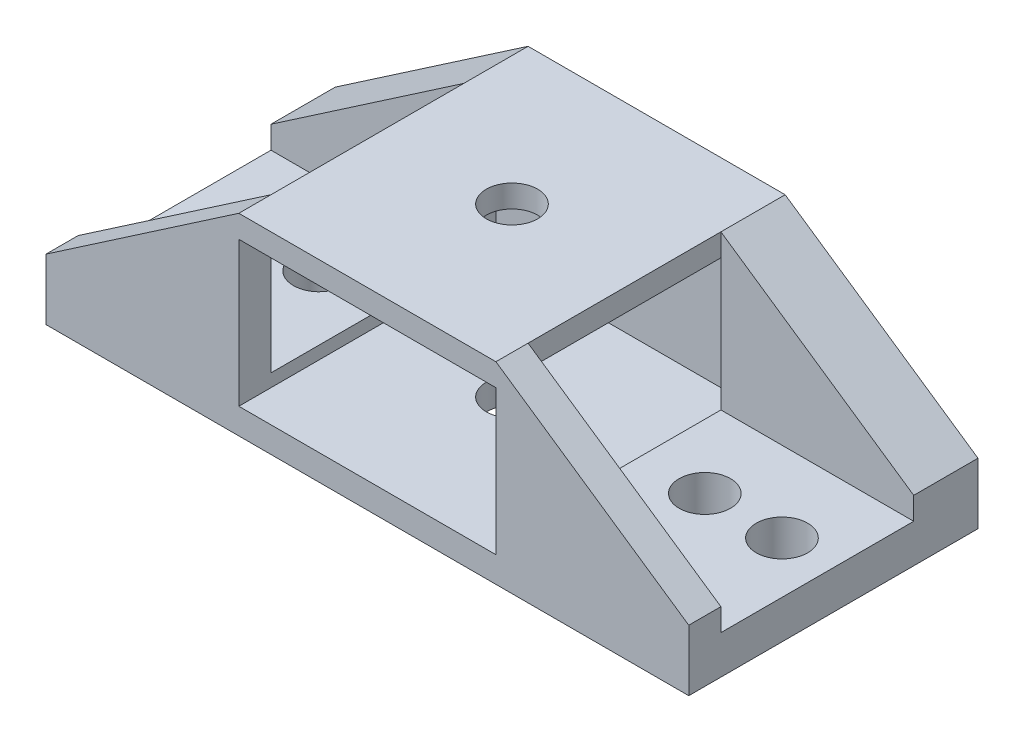
SolidWorks part; units mm, degrees
ref_plane "Front Plane" through (0, 0, 0) normal (0, 0, 1) x (1, 0, 0)
ref_plane "Top Plane" through (0, 0, 0) normal (0, 1, 0) x (1, 0, 0)
ref_plane "Right Plane" through (0, 0, 0) normal (1, 0, 0) x (0, 0, -1)
sketch "Sketch1" plane through (0, 0, 0) normal (0, 1, 0) x (1, 0, 0)
  line L0 (0, 11.25) -> (50, 11.25) construction
  line L1 (0, 0) -> (50, 0)
  line L2 (0, 0) -> (0, 22.5)
  line L3 (0, 22.5) -> (50, 22.5)
  line L4 (50, 0) -> (50, 22.5)
  line L5 (15, 22.5) -> (35, 22.5)
  line L6 (15, 22.5) -> (15, 0)
  line L7 (15, 0) -> (35, 0)
  line L8 (35, 22.5) -> (35, 0)
  circle A0 centre (4, 11.25) radius 2
  circle A1 centre (10, 11.25) radius 2
  circle A2 centre (40, 11.25) radius 2
  circle A3 centre (46, 11.25) radius 2
  point P19 (69.6045, -7.2844)
  dimension "D5" = 4
  dimension "D6" = 30
  dimension "D7" = 4
  dimension "D8" = 4
  dimension "D2" = 50
  dimension "D3" = 20
  dimension "D4" = 15
  dimension "D9" = 6
  dimension "D10" = 22.5
extrude "Boss-Extrude1" add sketch "Sketch1" along normal blind 3 contours L2 L0 A0 A1 L6 L3 | L0 L2 L1 L6 A1 A0 | L0 L6 L1 L8 | L6 L0 L8 L3 | L0 L8 L1 L4 A3 A2 | L8 L0 A2 A3 L4 L3 region at (42.4598, 0, -17.2593) region at (42.4598, 0, -5.2407) region at (25, 0, -5.625) region at (25, 0, -16.875) region at (7.5402, 0, -5.2407) region at (7.5402, 0, -17.2593)
extrude "Boss-Extrude2" add sketch "Sketch1<3>" along normal blind 15 contours L0 L6 L1 L8 | L6 L0 L8 L3 region at (25, 0, -5.625) region at (25, 0, -16.875)
sketch "Sketch1<3>" plane through (0, 0, 0) normal (0, 1, 0) x (1, 0, 0) same geometry as "Sketch1"
sketch "Sketch2" plane through (0, 0, 0) normal (0, 0, 1) x (1, 0, 0)
  line L0 (15, 13.25) -> (35, 13.25)
  line L1 (15, 15) -> (35, 15)
  line L2 (15, 15) -> (15, 3)
  line L3 (15, 3) -> (35, 3)
  line L4 (35, 15) -> (35, 3)
  line L6 (15, 3) -> (35, 3)
  line L7 (15, 3) -> (15, 2)
  line L8 (15, 2) -> (35, 2)
  line L9 (35, 3) -> (35, 2)
  line M8 (15, 15) -> (15, 3)
  dimension "D1" = 1.75
  dimension "D2" = 1
extrude "Cut-Extrude1" cut sketch "Sketch2" against normal blind 20 contours L4 L0 M8 | L9 L3 L7 L8 region at (25, 8.125, 0) region at (25, 2.5, 0)
sketch "Sketch3" plane through (0, 3, 0) normal (0, 1, 0) x (1, 0, 0)
  line L0 (15, 20) -> (15, 22.5) construction
  line L1 (0, 22.5) -> (15, 22.5)
  line L2 (0, 22.5) -> (0, 13)
  line L3 (15, 2.5) -> (0, 2.5)
  line L4 (15, 22.5) -> (15, 13)
  line L5 (25, 17.5) -> (25, 0) construction
  line L6 (35, 22.5) -> (35, 13)
  line L7 (50, 22.5) -> (35, 22.5)
  line L8 (50, 22.5) -> (50, 13)
  line L13 (15, 0) -> (35, 0)
  line L14 (35, 0) -> (35, 17.5)
  line L15 (35, 17.5) -> (15, 17.5)
  line L16 (15, 17.5) -> (15, 0)
  line L17 (0, 0) -> (0, 22.5) construction
  line L18 (15, 17.5) -> (0, 17.5)
  line L19 (0, 0) -> (15, 0)
  line L20 (35, 17.5) -> (50, 17.5)
  line L21 (0, 2.5) -> (0, 0)
  line L22 (50, 2.5) -> (50, 0)
  line L23 (50, 0) -> (35, 0)
  line L24 (35, 2.5) -> (50, 2.5)
  line M12 (0, 0) -> (15, 0)
  line M13 (15, 20) -> (15, 22.5)
  line M14 (15, 22.5) -> (0, 22.5)
  line M15 (0, 22.5) -> (0, 0)
  dimension "D2" = 2.5
  dimension "D3" = 17.5
  dimension "D1" = 20
extrude "Boss-Extrude3" add sketch "Sketch3" along normal up to surface (12 mm away) contours L18 L4 M14 M15 | L3 M13 M15 M12 | L6 L20 L8 L7 | L24 L14 L23 L22 region at (42.5, 3, -20) region at (7.5, 3, -20) region at (7.5, 3, -1.25) region at (42.5, 3, -1.25) up to face at (25, 15, -11.25)
sketch "Sketch4" plane through (0, 0, 0) normal (0, 0, 1) x (1, 0, 0)
  line L0 (15, 15) -> (0, 4.75)
  line L1 (0, 15) -> (50, 15) construction
  line L2 (25, 13.25) -> (25, 4.75) construction
  line L3 (0, 15) -> (0, 0) construction
  line L4 (35, 15) -> (50, 4.75)
  line L5 (50, 15) -> (50, 0) construction
  line L12 (35, 13.25) -> (15, 13.25)
  line L24 (35, 13.25) -> (15, 13.25)
  line L32 (15, 13.25) -> (15, 2)
  line L35 (15, 13.25) -> (15, 2)
  line L36 (15, 2) -> (35, 2)
  line L37 (15, 2) -> (35, 2)
  line L38 (35, 2) -> (35, 13.25)
  line L39 (35, 2) -> (35, 13.25)
  line M15 (50, 0) -> (50, 15)
  line M16 (50, 15) -> (0, 15)
  line M17 (0, 15) -> (0, 0)
  dimension "D1" = 0
extrude "Cut-Extrude2" cut sketch "Sketch4" against normal up to surface (22.5 mm away) contours M16 M17 | M16 M15 region at (45, 11.5833, 0) region at (5, 11.5833, 0) up to face at (25, 7.5, -22.5)
sketch "Sketch5" plane through (0, 15, 0) normal (0, 1, 0) x (1, 0, 0)
  line L1 (15, 17.5) -> (15, 2.5) construction
  line L3 (10, 11.25) -> (25, 11.25) construction
  circle A0 centre (25, 11.25) radius 2
  dimension "D3" = 4
  dimension "D2" = 10
extrude "Cut-Extrude3" cut sketch "Sketch5" against normal through all
